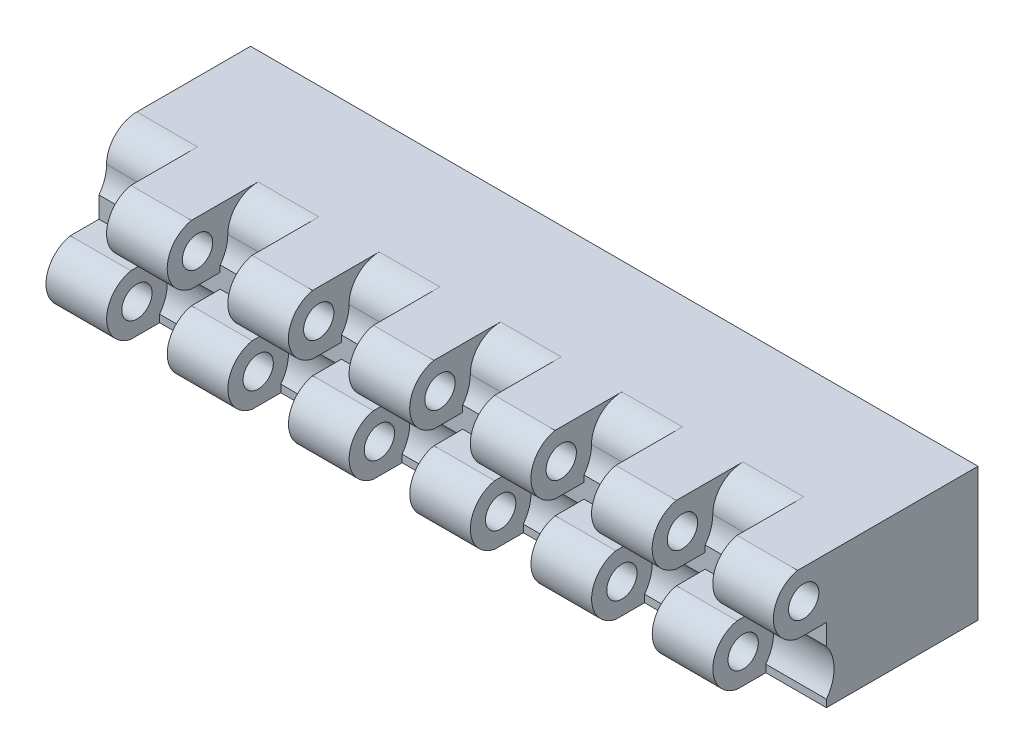
SolidWorks part; units mm, degrees
ref_plane "Front Plane" through (0, 0, 0) normal (0, 0, 1) x (1, 0, 0)
ref_plane "Top Plane" through (0, 0, 0) normal (0, 1, 0) x (1, 0, 0)
ref_plane "Right Plane" through (0, 0, 0) normal (1, 0, 0) x (0, 0, -1)
sketch "Sketch1" plane through (0, 0, 0) normal (1, 0, 0) x (0, 0, -1)
  line L1 (-12.5, 11) -> (12.5, 11)
  line L2 (-12.5, 11) -> (-12.5, -11)
  line L3 (-12.5, -11) -> (12.5, -11)
  line L4 (12.5, 11) -> (12.5, -11)
  line L5 (-12.5, 11) -> (12.5, -11) construction
  line L6 (-12.5, -11) -> (12.5, 11) construction
  point P0 (0, 0)
  dimension "D1" = 22
  dimension "D2" = 25
extrude "Boss-Extrude1" add sketch "Sketch1" along normal mid plane 120
sketch "Sketch5" plane through (60, 0, 0) normal (1, 0, 0) x (0, 0, -1)
  line L0 (-12.5, 11) -> (-12.5, 1.01) construction
  line L1 (-12.5, 11) -> (-12.5, -11) construction
  line L2 (-12.5, 6.005) -> (-17.5, 6.005) construction
  line L3 (-13.7433, 11) -> (-11.25, 11)
  line L7 (-11.25, 6.005) -> (-11.25, 11)
  arc A1 (-13.7433, 11) -> (-11.25, 6.005) centre (-17.5, 6.005) ccw
  dimension "D1" = 5
extrude "Cut-Extrude2" cut sketch "Sketch5" against normal up to next
sketch "Sketch6" plane through (-60, 0, 0) normal (-1, 0, 0) x (0, 0, 1)
  line L0 (12.5, -11) -> (12.5, -1.01) construction
  line L1 (12.5, 2.255) -> (12.5, -11) construction
  line L2 (12.5, -6.005) -> (17.5, -6.005) construction
  circle A0 centre (17.5, -6.005) radius 6.26
  dimension "D2" = 5
  dimension "D1" = 9.99
extrude "Cut-Extrude3" cut sketch "Sketch6" against normal up to next
fillet "Fillet1" radius 5 1 edges at (0, 11, 11.25)
sketch "Sketch2" plane through (60, 0, 0) normal (1, 0, 0) x (0, 0, -1)
  line L0 (-17.25, 1.202) -> (-6, 1.202)
  line L1 (-12.5, -11) -> (-12.5, 1.202) construction
  line L13 (-6, 11) -> (-6, 1.202)
  line L14 (-17.25, 11) -> (-6, 11)
  arc A1 (-17.25, 11) -> (-17.25, 1.202) centre (-16.25, 6.101) ccw
  circle A2 centre (-16.25, 6.101) radius 2.5
  dimension "D3" = 5
  dimension "D1" = 2.5
  dimension "D2" = 11.25
  dimension "D4" = 5
extrude "Boss-Extrude2" add sketch "Sketch2" against normal blind 10
pattern_linear "LPattern1" count 6 spacing 20 along (-1, 0, 0) of "Boss-Extrude2"
sketch "Sketch3" plane through (-60, 0, 0) normal (-1, 0, 0) x (0, 0, 1)
  line L0 (10.99, -1.202) -> (17.24, -1.202)
  line L1 (17.24, -11) -> (10.99, -11)
  line L8 (10.99, -11) -> (10.99, -1.202)
  arc A1 (17.24, -11) -> (17.24, -1.202) centre (16.24, -6.101) ccw
  circle A2 centre (16.24, -6.101) radius 2.5
  arc A3 (12.5, -2.2384) -> (12.5, -9.7716) centre (17.5, -6.005) ccw construction
  point P7 (12.24, -0.3112)
  point P8 (11.24, -6.005)
  dimension "D2" = 4
  dimension "D3" = 5
  dimension "D4" = 2.5
  dimension "D1" = 6.25
  dimension "D5" = 5
extrude "Boss-Extrude3" add sketch "Sketch3" against normal blind 10 contours A1 A2 region at (-60, -1.3438, 14.115)
pattern_linear "LPattern2" count 6 spacing 20 along (1, 0, 0) of "Boss-Extrude3"
sketch "Sketch4" plane through (0, 0, -12.5) normal (0, 0, -1) x (-1, 0, 0)
  circle A0 centre (0, 0) radius 7
  dimension "D1" = 14
extrude "Cut-Extrude1" cut sketch "Sketch4" against normal blind 15
